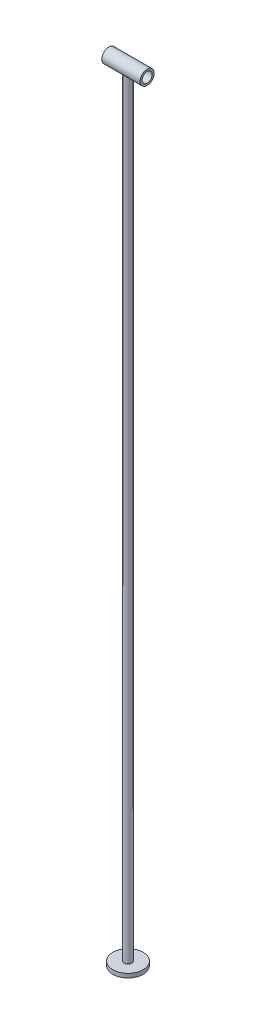
SolidWorks part; units mm, degrees
material "Plain Carbon Steel"
ref_plane "Front Plane" through (0, 0, 0) normal (0, 0, 1) x (1, 0, 0)
ref_plane "Top Plane" through (0, 0, 0) normal (0, 1, 0) x (1, 0, 0)
ref_plane "Right Plane" through (0, 0, 0) normal (1, 0, 0) x (0, 0, -1)
sketch "klip_Sketch1" plane through (0, 0, 0) normal (0, 1, 0) x (1, 0, 0)
  circle A0 centre (0, 0) radius 75
  dimension "D1" = 150
extrude "klip_Boss-Extrude1" add sketch "klip_Sketch1" against normal blind 20 contours A0
sketch "klip_Sketch3" plane through (0, 0, 0) normal (1, 0, 0) x (0, 0, -1)
  circle A0 centre (0, 3835) radius 35
  circle A1 centre (0, 3835) radius 25
  dimension "D3" = 50
  dimension "D1" = 70
  dimension "D2" = 3835
extrude "klip_Boss-Extrude3" add sketch "klip_Sketch3" along normal blind 95 and the other way blind 95 separate body
sketch "klip_Sketch2" plane through (0, 0, 0) normal (0, 1, 0) x (1, 0, 0)
  circle A0 centre (0, 0) radius 18.75
  dimension "D1" = 37.5
extrude "klip_Boss-Extrude2" add sketch "klip_Sketch2" along normal up to surface (3805.446 mm away) contours A0 up to face at (-95, 3835, -35)
equation "\"sirina_klipa\"= 150"
equation "\"debljina_klipa\"= 20"
equation "\"sirina_klipnjace\"= \"sirina_klipa\" / 4"
equation "\"duljina_klipnjace\"= 3800"
equation "\"r2_v\"= 70"
equation "\"r2_u\"= 50"
equation "\"r1_v\"= 70"
equation "\"r1_u\"= 50"
equation "\"l2\" = 190"
equation "\"l1\" = 230"
equation "\"sirina_cilindra\"= \"sirina_klipa\" + \"debljina_stijenke\" * 2"
equation "\"duljina_komore\"= 30"
equation "\"debljina_stijenke\"= 10"
equation "\"D3@cilindar_Sketch1\"= \"duljina_komore\""
equation "\"D4@cilindar_Sketch1\"=\"sirina_klipa\"/2"
equation "\"D1@cilindar_Sketch1\"=\"sirina_cilindra\"/2"
equation "\"D2@cilindar_Sketch1\"= \"duljina_cilindra\""
equation "\"D1@cilindar_Shell1\"=\"debljina_stijenke\""
equation "\"duljina_cilindra\"= \"duljina_klipnjace\" + \"debljina_klipa\" + \"debljina_stijenke\" - \"duljina_komore\""
equation "\"D1@cilindar_Sketch2\"=\"duljina_cilindra\"/2 + \"duljina_komore\" + \"r1_v\"/2 + 1"
equation "\"D2@cilindar_Sketch2\"=\"r1_v\""
equation "\"D3@cilindar_Sketch2\"=\"r1_u\""
equation "\"D1@cilindar_Sketch7\" = \"sirina_klipnjace\""
equation "\"D2@cilindar_Boss-Extrude1\"=\"l1\"/2"
equation "\"D1@cilindar_Boss-Extrude1\"=\"l1\"/2"
equation "\"D1@klip_Boss-Extrude1\"=\"debljina_klipa\""
equation "\"D1@klip_Sketch1\"=\"sirina_klipa\""
equation "\"D2@klip_Sketch3\"= \"duljina_klipnjace\" + \"r2_v\" / 2"
equation "\"D3@klip_Sketch3\" = \"r2_u\""
equation "\"D1@klip_Sketch3\"=\"r2_v\""
equation "\"D1@klip_Boss-Extrude3\" = \"l2\" / 2"
equation "\"D2@klip_Boss-Extrude3\" = \"l2\" / 2"
equation "\"D1@klip_Sketch2\"=\"sirina_klipnjace\""
